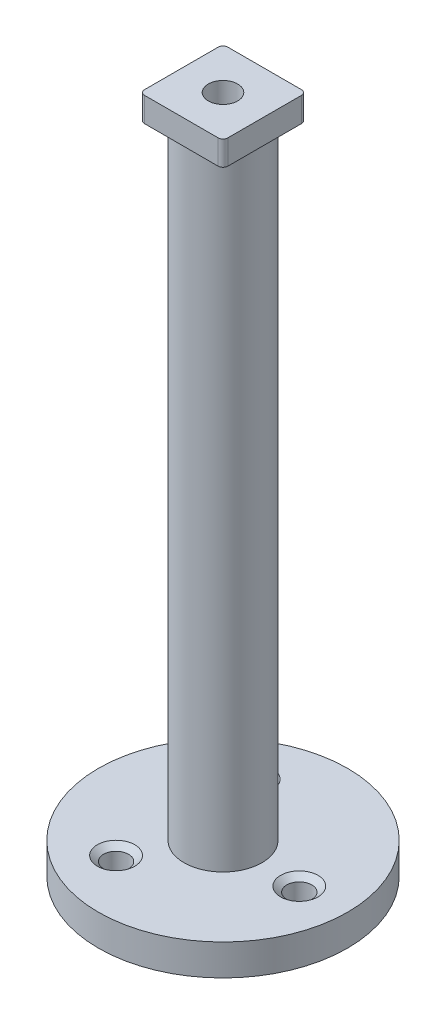
SolidWorks part; units mm, degrees
ref_plane "Front Plane" through (0, 0, 0) normal (0, 0, 1) x (1, 0, 0)
ref_plane "Top Plane" through (0, 0, 0) normal (0, 1, 0) x (1, 0, 0)
ref_plane "Right Plane" through (0, 0, 0) normal (1, 0, 0) x (0, 0, -1)
sketch "Sketch1" plane through (0, 0, 0) normal (0, 0, 1) x (1, 0, 0)
  line L0 (0, 131.177) -> (0, -23.3839) construction
  line L1 (0, 0) -> (25.4, 0)
  line L2 (25.4, 0) -> (25.4, 6.35)
  line L3 (25.4, 6.35) -> (7.9375, 6.35)
  line L4 (7.9375, 6.35) -> (7.9375, 133.35)
  line L8 (0, 133.35) -> (0, 0)
  line L9 (0, 133.35) -> (7.9375, 133.35)
  dimension "D1" = 50.8
  dimension "D2" = 6.35
  dimension "D3" = 15.875
  dimension "D4" = 127
revolve "Revolve1" add sketch "Sketch1" angle 360 about L0
sketch "Sketch2" plane through (0, 0, 0) normal (0, 1, 0) x (1, 0, 0)
  circle A0 centre (0, 0) radius 7.1438
  dimension "D1" = 14.2875
extrude "Cut-Extrude1" cut sketch "Sketch2" along normal offset from surface (120.65 mm away) 12.7 up to face at (0, 133.35, 7.9375)
sketch "Sketch5" plane through (0, 133.35, 0) normal (0, 1, 0) x (1, 0, 0)
  line L1 (-8.5, 8.5) -> (8.5, 8.5)
  line L2 (-8.5, 8.5) -> (-8.5, -8.5)
  line L3 (-8.5, -8.5) -> (8.5, -8.5)
  line L4 (8.5, 8.5) -> (8.5, -8.5)
  line L5 (-8.5, 8.5) -> (8.5, -8.5) construction
  line L6 (-8.5, -8.5) -> (8.5, 8.5) construction
  point P0 (0, 0)
  dimension "D1" = 17
  dimension "D2" = 17
extrude "Boss-Extrude3" add sketch "Sketch5" along normal blind 5
sketch "Sketch4" plane through (0, 138.35, 0) normal (0, 1, 0) x (1, 0, 0)
  circle A0 centre (0, 0) radius 3
  dimension "D1" = 6
extrude "Cut-Extrude2" cut sketch "Sketch4" against normal through all
fillet "Fillet1" radius 1 4 edges at (8.5, 135.85, 8.5) (-8.5, 135.85, 8.5) (8.5, 135.85, -8.5) (-8.5, 135.85, -8.5)
fillet "Fillet2" radius 0.25 1 edges at (0, 133.35, 7.9375)
hole_wizard "1/4-20 Tapped Hole1" positions "Sketch8" profile "Sketch9" tap size "1/4-20" standard "ANSI Inch" end condition through all
sketch "Sketch8" plane through (0, 6.35, 0) normal (0, 1, 0) x (1, 0, 0)
  circle A0 centre (0, 0) radius 15.875 construction
  point P7 (-7.6595, 13.905)
  point P17 (15.8718, -0.3192)
  point P18 (-8.2123, -13.5858)
  dimension "D1" = 31.75
  dimension "D2" = 3
sketch "Sketch9" plane through (-8.2123, 6.35, 13.5858) normal (1, 0, 0) x (0, 0, 1)
  line L0 (0, 0) -> (0, 6.35)
  line L1 (0, 6.35) -> (2.5527, 6.35)
  line L2 (2.5527, 6.35) -> (2.5527, 1.055)
  line L3 (2.5527, 1.055) -> (3.81, 0)
  line L5 (3.81, 0) -> (0, 0)
  line L6 (-2.5527, 1.055) -> (-3.81, 0) construction
  line L11 (0, -6.35) -> (0, 107.95) construction
  dimension "Thru Tap Drill Dia." = 5.1054
  dimension "Thru Tap Drill Depth" = 6.35
  dimension "Near C'Sink Dia." = 7.62
  dimension "Near C'Sink Angle" = 100
cosmetic thread "Hole Thread1" parameters "D2"=6.35
cosmetic thread "Hole Thread2" parameters "D2"=6.35
cosmetic thread "Hole Thread3" parameters "D2"=6.35
